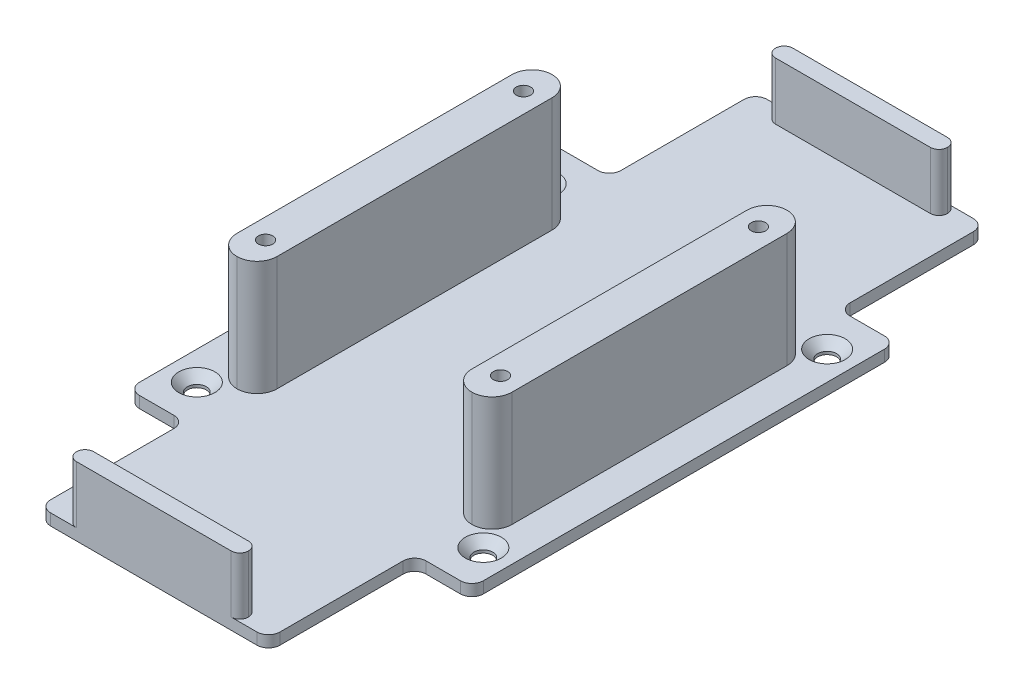
SolidWorks part; units mm, degrees
ref_plane "Спереди" through (0, 0, 0) normal (0, 0, 1) x (1, 0, 0)
ref_plane "Сверху" through (0, 0, 0) normal (0, 1, 0) x (1, 0, 0)
ref_plane "Справа" through (0, 0, 0) normal (1, 0, 0) x (0, 0, -1)
sketch "Эскиз1" plane through (0, 0, 0) normal (0, 1, 0) x (1, 0, 0)
  line L0 (0, 62.5) -> (0, -62.5) construction
  line L1 (-30, 62.5) -> (30, 62.5)
  line L2 (-30, 62.5) -> (-30, -62.5)
  line L3 (-30, -62.5) -> (30, -62.5)
  line L4 (30, 62.5) -> (30, -62.5)
  line L6 (-30, 0) -> (30, 0) construction
  point P8 (0, 0)
  dimension "D1" = 60
  dimension "D2" = 125
extrude "тело" add sketch "Эскиз1" along normal blind 2
sketch "Эскиз4" plane through (0, 2, 0) normal (0, 1, 0) x (1, 0, 0)
  line L0 (0, 62.5) -> (0, -62.5) construction
  line L1 (30, 62.5) -> (-30, 62.5) construction
  line L2 (-30, -62.5) -> (30, -62.5) construction
  line L3 (-25, 30) -> (25, -30) construction
  line L4 (-30, 62.5) -> (-30, -62.5) construction
  line L5 (-30, 0) -> (30, 0) construction
  line L6 (30, -62.5) -> (30, 62.5) construction
  line L7 (-25, 30) -> (25, 30) construction
  line L8 (-25, 30) -> (-25, -30) construction
  line L9 (-25, -30) -> (25, -30) construction
  line L10 (25, 30) -> (25, -30) construction
  circle A0 centre (-25, 30) radius 1.65
  circle A1 centre (25, 30) radius 1.65
  circle A2 centre (25, -30) radius 1.65
  circle A3 centre (-25, -30) radius 1.65
  point P20 (0, 0)
  dimension "D1" = 3.3
  dimension "D2" = 50
  dimension "D3" = 60
extrude "крепление к этажу" cut sketch "Эскиз4" against normal through all
sketch "Эскиз6" plane through (0, 2, 0) normal (0, 1, 0) x (1, 0, 0)
  line L0 (0, 62.5) -> (0, -62.5) construction
  line L1 (30, 62.5) -> (-30, 62.5) construction
  line L2 (-30, -62.5) -> (30, -62.5) construction
  line L3 (-25, 30) -> (-25, 37) construction
  line L4 (-30, 62.5) -> (-30, -62.5) construction
  line L5 (-30, 0) -> (30, 0) construction
  line L6 (30, -62.5) -> (30, 62.5) construction
  line L7 (-30, 62.5) -> (-20, 62.5)
  line L8 (-30, 62.5) -> (-30, 37)
  line L9 (-30, 37) -> (-20, 37)
  line L10 (-20, 62.5) -> (-20, 37)
  line L11 (30, 62.5) -> (20, 62.5)
  line L12 (30, 62.5) -> (30, 37)
  line L13 (30, 37) -> (20, 37)
  line L14 (20, 62.5) -> (20, 37)
  line L15 (30, -62.5) -> (20, -62.5)
  line L16 (30, -62.5) -> (30, -37)
  line L17 (30, -37) -> (20, -37)
  line L18 (20, -62.5) -> (20, -37)
  line L19 (-30, -62.5) -> (-20, -62.5)
  line L20 (-30, -62.5) -> (-30, -37)
  line L21 (-30, -37) -> (-20, -37)
  line L22 (-20, -62.5) -> (-20, -37)
  dimension "D1" = 7
extrude "вырезы под винты соседних плат" cut sketch "Эскиз6" against normal through all
sketch "Эскиз2" plane through (0, 2, 0) normal (0, 1, 0) x (1, 0, 0)
  line L0 (0, 62.5) -> (0, -62.5) construction
  line L3 (20, 62.5) -> (-20, 62.5) construction
  line L5 (-20, -62.5) -> (20, -62.5) construction
  line L7 (-30, 0) -> (30, 0) construction
  line L8 (-30, 37) -> (-30, -37) construction
  line L9 (30, -37) -> (30, 37) construction
  line L11 (-15, 62.5) -> (15, 62.5)
  line L12 (-15, 62.5) -> (-15, 59.5)
  line L13 (-15, 59.5) -> (15, 59.5)
  line L14 (15, 62.5) -> (15, 59.5)
  line L15 (-15, -62.5) -> (15, -62.5)
  line L16 (-15, -62.5) -> (-15, -59.5)
  line L17 (-15, -59.5) -> (15, -59.5)
  line L18 (15, -62.5) -> (15, -59.5)
  point P22 (0, 62.5)
  point P23 (0, -62.5)
  dimension "D1" = 119
  dimension "D2" = 30
extrude "выступы фиксации аккума" add sketch "Эскиз2" along normal blind 10
sketch "Эскиз9" plane through (0, 2, 0) normal (0, 1, 0) x (1, 0, 0)
  line L0 (0, 62.5) -> (0, -62.5) construction
  line L3 (-30, 0) -> (30, 0) construction
  line L5 (-30, 37) -> (-30, -37) construction
  line L6 (30, -37) -> (30, 37) construction
  line L7 (15, 62.5) -> (-15, 62.5) construction
  line L8 (-24, 27.5) -> (-17, 27.5)
  line L9 (-24, 27.5) -> (-24, -27.5)
  line L10 (-24, -27.5) -> (-17, -27.5)
  line L11 (-17, 27.5) -> (-17, -27.5)
  line L12 (24, 27.5) -> (17, 27.5)
  line L13 (24, 27.5) -> (24, -27.5)
  line L14 (24, -27.5) -> (17, -27.5)
  line L15 (17, 27.5) -> (17, -27.5)
  line L16 (-15, -62.5) -> (15, -62.5) construction
  point P20 (17, 0)
  point P21 (-17, 0)
  point P28 (0, 62.5)
  dimension "D1" = 34
  dimension "D2" = 55
  dimension "D3" = 7
extrude "выступы для крышки" add sketch "Эскиз9" along normal blind 20
sketch "Эскиз11" plane through (0, 22, 0) normal (0, 1, 0) x (1, 0, 0)
  line L0 (-20.5, 27.5) -> (-20.5, -27.5) construction
  line L1 (-17, 27.5) -> (-24, 27.5) construction
  line L2 (-24, -27.5) -> (-17, -27.5) construction
  line L4 (24, 27.5) -> (17, 27.5) construction
  line L5 (20.5, 27.5) -> (20.5, -27.5) construction
  line L6 (17, -27.5) -> (24, -27.5) construction
  line L8 (24, -27.5) -> (24, 27.5) construction
  line L9 (24, 0) -> (-24, 0) construction
  line L10 (-24, 27.5) -> (-24, -27.5) construction
  circle A0 centre (-20.5, 22.5) radius 1.25
  circle A1 centre (-20.5, -22.5) radius 1.25
  circle A2 centre (20.5, 22.5) radius 1.25
  circle A3 centre (20.5, -22.5) radius 1.25
  dimension "D2" = 2.5
  dimension "D1" = 45
extrude "отверстия под шурупы" cut sketch "Эскиз11" against normal blind 15
chamfer "Фаска1" distance 1.5 angle 45 4 edges at (25, 2, -28.35) (-25, 2, 31.65) (25, 2, 31.65) (-25, 2, -28.35)
fillet "Скругление1" radius 1.5 8 edges at (15, 7, -59.5) (15, 7, -62.5) (-15, 7, -62.5) (-15, 7, -59.5) (15, 7, 62.5) (15, 7, 59.5) (-15, 7, 59.5) (-15, 7, 62.5)
fillet "Скругление5" radius 2 12 edges at (-30, 1, 37) (-20, 1, 37) (-20, 1, 62.5) (-30, 1, -37) (-20, 1, -37) (-20, 1, -62.5) (20, 1, -62.5) (20, 1, -37) (30, 1, -37) (30, 1, 37) (20, 1, 37) (20, 1, 62.5)
fillet "Скругление6" radius 3.5 8 edges at (-24, 11.7713, -27.5) (-17, 12, -27.5) (17, 12, -27.5) (24, 11.7713, -27.5) (24, 11.7713, 27.5) (17, 12, 27.5) (-17, 12, 27.5) (-24, 11.7713, 27.5)
